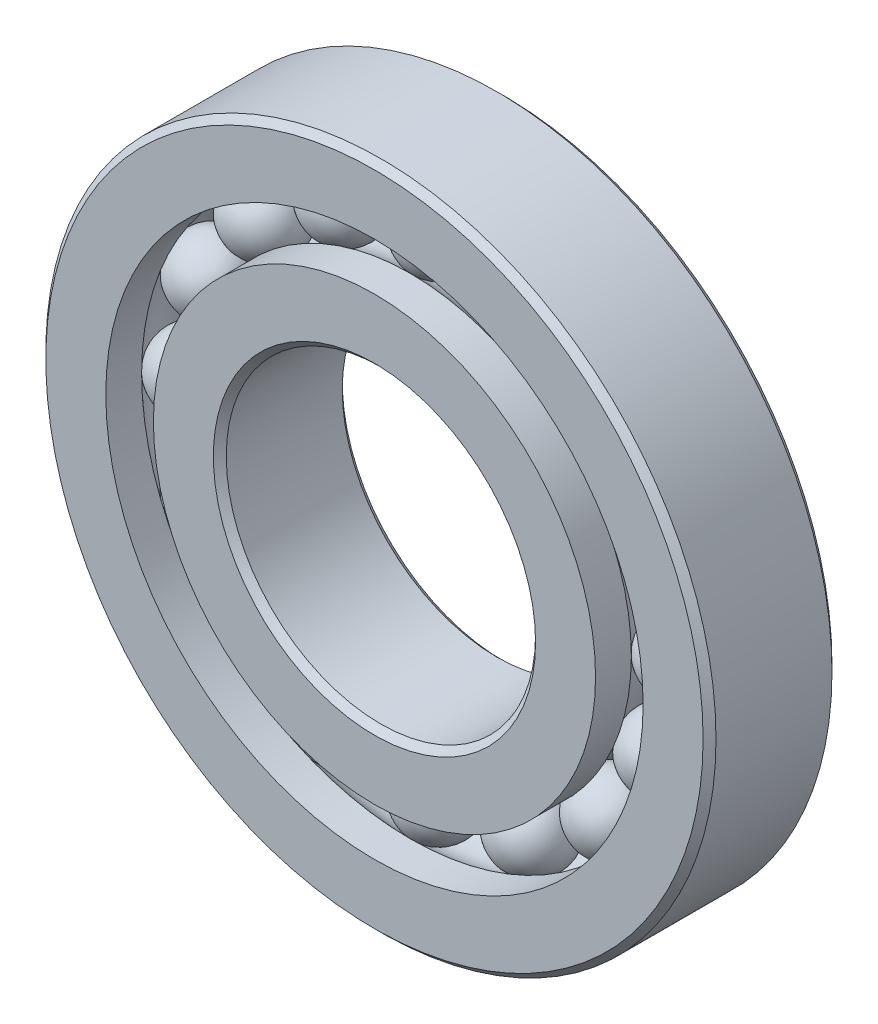
SolidWorks part; units mm, degrees
material "Delrin 2700 NC010, Low Viscosity Acetal Copolymer (SS)"
ref_plane "Front Plane" through (0, 0, 0) normal (0, 0, 1) x (1, 0, 0)
ref_plane "Top Plane" through (0, 0, 0) normal (0, 1, 0) x (1, 0, 0)
ref_plane "Right Plane" through (0, 0, 0) normal (1, 0, 0) x (0, 0, -1)
sketch "Sketch1" plane through (0, 0, 0) normal (1, 0, 0) x (0, 0, -1)
  line L0 (-3.9688, 0) -> (3.9688, 0) construction
  line L1 (0, 20.6375) -> (0, -20.6375) construction
  line L2 (3.5719, 20.6375) -> (-3.5719, 20.6375)
  line L3 (-3.5719, 20.6375) -> (-3.9688, 20.2406)
  line L4 (-3.9688, 20.2406) -> (-3.9688, 16.5466)
  line L5 (-3.9688, 16.5466) -> (-1.7639, 16.5466)
  line L6 (3.9688, 16.5466) -> (1.7639, 16.5466)
  line L7 (3.9688, 20.2406) -> (3.9688, 16.5466)
  line L8 (3.5719, 20.6375) -> (3.9688, 20.2406)
  line L9 (0, 20.6375) -> (0, 15.0813) construction
  line L10 (0, 15.0813) -> (0, 9.525) construction
  arc A0 (-1.7639, 16.5466) -> (1.7639, 16.5466) centre (0, 15.0813) cw
  point P14 (0, 9.525)
  dimension "D3" = 3.5278
  dimension "D1" = 45
  dimension "Width" = 7.9375
  dimension "OD" = 41.275
  dimension "D2" = 0.3969
  dimension "Shaft Dia" = 19.05
  dimension "D4" = 1.4654
revolve "Revolve1" add sketch "Sketch1" angle 360 about L0
sketch "Sketch3" plane through (0, 0, 0) normal (1, 0, 0) x (0, 0, -1)
  line L0 (-3.9688, 13.6159) -> (-1.7639, 13.6159)
  line L1 (0, 20.6375) -> (0, -20.6375) construction
  line L2 (-3.9688, 20.2406) -> (-3.9688, 16.5466) construction
  line L3 (-3.9688, 13.6159) -> (-3.9688, 9.9219)
  line L4 (-3.5719, 20.6375) -> (-3.9688, 20.2406) construction
  line L5 (-3.9688, 9.9219) -> (-3.5719, 9.525)
  line L6 (-3.5719, 9.525) -> (3.5719, 9.525)
  line L7 (3.5719, 20.6375) -> (3.5719, -20.6375) construction
  line L8 (3.5719, 9.525) -> (3.9688, 9.9219)
  line L9 (3.9688, -20.2406) -> (3.9688, 20.2406) construction
  line L10 (3.9688, 9.9219) -> (3.9688, 13.6159)
  line L11 (3.9688, 13.6159) -> (1.7639, 13.6159)
  line L13 (3.5719, 20.6375) -> (3.9688, 20.2406) construction
  arc A0 (1.7639, 16.5466) -> (-1.7639, 16.5466) centre (0, 15.0813) ccw construction
  arc A1 (1.7639, 13.6159) -> (-1.7639, 13.6159) centre (0, 15.0812) cw
revolve "Revolve3" add sketch "Sketch3" angle 360 about L0
sketch "Sketch4" plane through (0, 0, 0) normal (1, 0, 0) x (0, 0, -1)
  line L0 (-2.2932, 15.0813) -> (2.2932, 15.0813)
  arc A2 (-2.2932, 15.0813) -> (2.2932, 15.0813) centre (0, 15.0813) cw
  arc A3 (1.7639, 16.5466) -> (-1.7639, 16.5466) centre (0, 15.0813) ccw construction
revolve "Revolve4" add sketch "Sketch4" angle 360 about L0
ref_axis "Axis1" through (0, 0, -3.9688) along (0, 0, 1)
pattern_circular "CirPattern1" count 16 every 22.5 about axis through (0, 0, -3.9688) along (0, 0, 1) of bodies 104
equation "\"D2@Sketch1\" = \"Width@Sketch1\"*.05"
equation "\"D3@Sketch1\" = \"Width@Sketch1\"/2.25"
equation "\"D4@Sketch1\" = (((\"OD@Sketch1\"-\"Width@Sketch1\")/2)/3.25)/3.5"
equation "\"D2@CirPattern1\" = 360/\"Balls@CirPattern1\""
